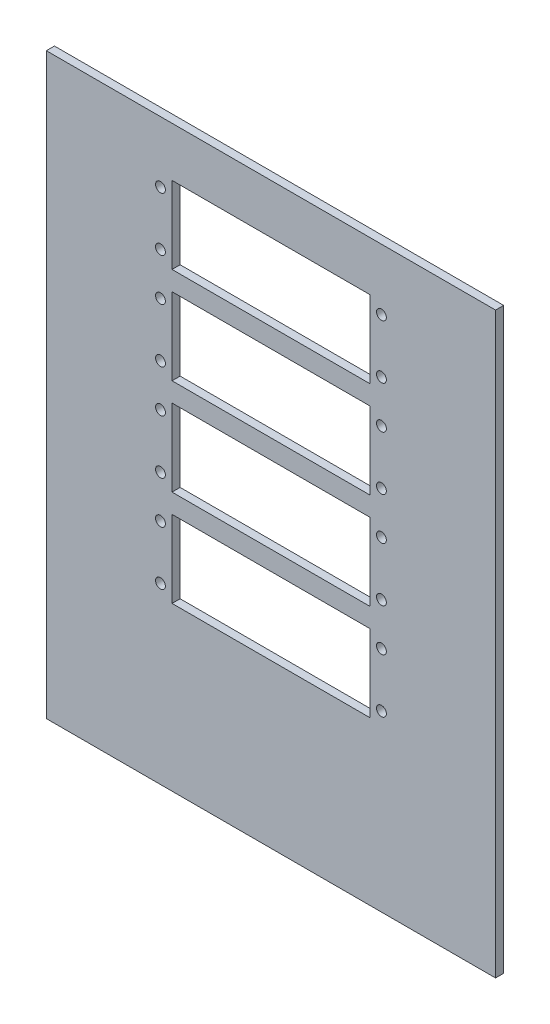
SolidWorks part; units mm, degrees
ref_plane "Plan de face" through (0, 0, 0) normal (0, 0, 1) x (1, 0, 0)
ref_plane "Plan de dessus" through (0, 0, 0) normal (0, 1, 0) x (1, 0, 0)
ref_plane "Plan de droite" through (0, 0, 0) normal (1, 0, 0) x (0, 0, -1)
sketch "Esquisse1" plane through (0, 0, 0) normal (0, 0, 1) x (1, 0, 0)
  line L1 (-161.8321, 173.5369) -> (71.1679, 173.5369)
  line L2 (-161.8321, 173.5369) -> (-161.8321, -126.4631)
  line L3 (-161.8321, -126.4631) -> (71.1679, -126.4631)
  line L4 (71.1679, 173.5369) -> (71.1679, -126.4631)
  dimension "D1" = 300
  dimension "D2" = 233
extrude "Boss.-Extru.1" add sketch "Esquisse1" along normal blind 4.2
sketch "Esquisse2" plane through (0, 0, 4.2) normal (0, 0, 1) x (1, 0, 0)
  line L1 (-96.6321, -2.1231) -> (5.9679, -2.1231)
  line L2 (-96.6321, -2.1231) -> (-96.6321, -42.1231)
  line L3 (-96.6321, -42.1231) -> (5.9679, -42.1231)
  line L4 (5.9679, -2.1231) -> (5.9679, -42.1231)
  line L5 (71.1679, -126.4631) -> (71.1679, 173.5369) construction
  line L6 (-96.6321, 47.8769) -> (5.9679, 47.8769)
  line L7 (-96.6321, 47.8769) -> (-96.6321, 7.8769)
  line L8 (-96.6321, 7.8769) -> (5.9679, 7.8769)
  line L9 (5.9679, 47.8769) -> (5.9679, 7.8769)
  line L10 (-96.6321, 97.8769) -> (5.9679, 97.8769)
  line L11 (-96.6321, 97.8769) -> (-96.6321, 57.8769)
  line L12 (-96.6321, 57.8769) -> (5.9679, 57.8769)
  line L13 (5.9679, 97.8769) -> (5.9679, 57.8769)
  line L14 (-96.6321, 147.8769) -> (5.9679, 147.8769)
  line L15 (-96.6321, 147.8769) -> (-96.6321, 107.8769)
  line L16 (-96.6321, 107.8769) -> (5.9679, 107.8769)
  line L17 (5.9679, 147.8769) -> (5.9679, 107.8769)
  line L18 (-161.8321, -126.4631) -> (71.1679, -126.4631) construction
  circle A0 centre (-102.6321, -8.1231) radius 2.55
  circle A1 centre (11.9679, -8.1231) radius 2.55
  circle A2 centre (-102.6321, 41.8769) radius 2.55
  circle A3 centre (11.9679, 41.8769) radius 2.55
  circle A4 centre (-102.6321, 91.8769) radius 2.55
  circle A5 centre (11.9679, 91.8769) radius 2.55
  circle A6 centre (-102.6321, 141.8769) radius 2.55
  circle A7 centre (11.9679, 141.8769) radius 2.55
  circle A8 centre (-102.6321, 113.8769) radius 2.55
  circle A9 centre (11.9679, 113.8769) radius 2.55
  circle A10 centre (-102.6321, 63.8769) radius 2.55
  circle A11 centre (11.9679, 63.8769) radius 2.55
  circle A12 centre (-102.6321, 13.8769) radius 2.55
  circle A13 centre (11.9679, 13.8769) radius 2.55
  circle A14 centre (-102.6321, -36.1231) radius 2.55
  circle A15 centre (11.9679, -36.1231) radius 2.55
  dimension "D17" = 5.1
  dimension "D20" = 5.1
  dimension "D23" = 5.1
  dimension "D24" = 5.1
  dimension "D30" = 5.1
  dimension "D32" = 5.1
  dimension "D35" = 5.1
  dimension "D38" = 5.1
  dimension "D42" = 5.1
  dimension "D45" = 5.1
  dimension "D47" = 5.1
  dimension "D51" = 5.1
  dimension "D54" = 5.1
  dimension "D56" = 5.1
  dimension "D61" = 5.1
  dimension "D63" = 5.1
  dimension "D1" = 102.6
  dimension "D2" = 40
  dimension "D3" = 65.2
  dimension "D4" = 0
  dimension "D5" = 10
  dimension "D6" = 40
  dimension "D7" = 102.6
  dimension "D8" = 40
  dimension "D9" = 102.6
  dimension "D10" = 40
  dimension "D11" = 102.6
  dimension "D12" = 0
  dimension "D13" = 10
  dimension "D14" = 10
  dimension "D15" = 0
  dimension "D16" = 84.34
  dimension "D18" = 6
  dimension "D19" = 6
  dimension "D21" = 6
  dimension "D22" = 6
  dimension "D25" = 6
  dimension "D26" = 6
  dimension "D27" = 6
  dimension "D28" = 6
  dimension "D29" = 6
  dimension "D31" = 6
  dimension "D33" = 6
  dimension "D34" = 6
  dimension "D36" = 6
  dimension "D37" = 6
  dimension "D39" = 6
  dimension "D40" = 6
  dimension "D41" = 6
  dimension "D43" = 6
  dimension "D44" = 6
  dimension "D46" = 6
  dimension "D48" = 6
  dimension "D49" = 6
  dimension "D50" = 6
  dimension "D52" = 6
  dimension "D53" = 6
  dimension "D55" = 6
  dimension "D57" = 6
  dimension "D58" = 6
  dimension "D59" = 6
  dimension "D60" = 6
  dimension "D62" = 6
  dimension "D64" = 6
extrude "Enlèv. mat.-Extru.1" cut sketch "Esquisse2" against normal through all and the other way through all
